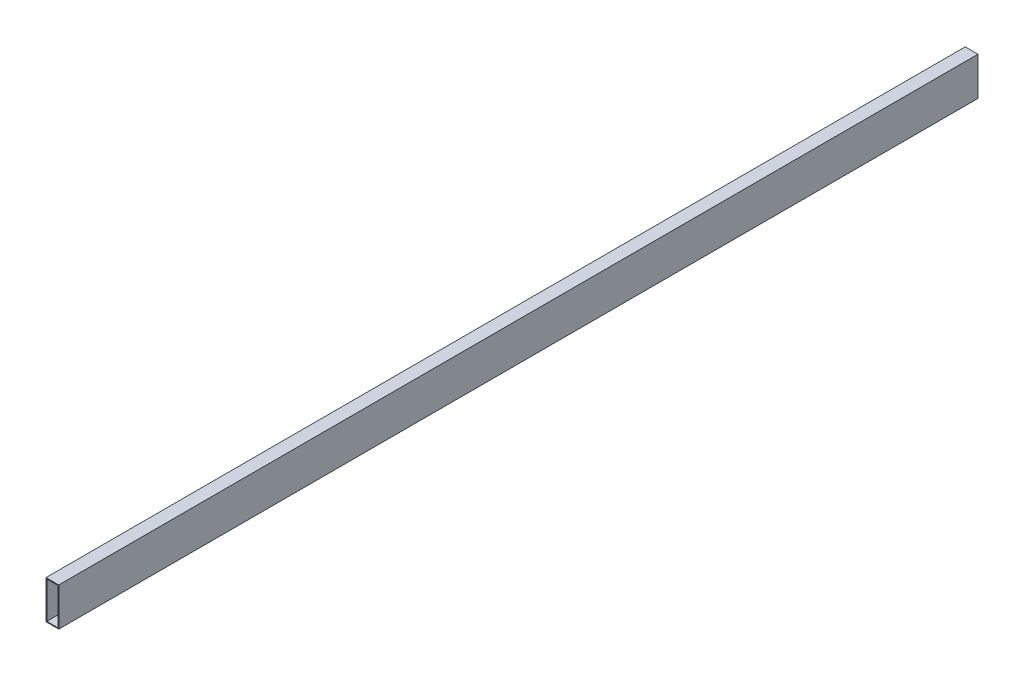
SolidWorks part; units mm, degrees
ref_plane "Front Plane" through (0, 0, 0) normal (0, 0, 1) x (1, 0, 0)
ref_plane "Top Plane" through (0, 0, 0) normal (0, 1, 0) x (1, 0, 0)
ref_plane "Right Plane" through (0, 0, 0) normal (1, 0, 0) x (0, 0, -1)
sketch "Sketch1" plane through (0, 0, 0) normal (0, 0, 1) x (1, 0, 0)
  line L1 (0, 0) -> (50.8, 0)
  line L2 (0, 0) -> (0, 152.4)
  line L3 (0, 152.4) -> (50.8, 152.4)
  line L4 (50.8, 0) -> (50.8, 152.4)
  dimension "D1" = 50.8
  dimension "D2" = 152.4
extrude "Boss-Extrude1" add sketch "Sketch1" along normal blind 3657.6
shell "Shell1" thickness 3.175 removed face at (25.4, 76.2, 3657.6) removed face at (25.4, 76.2, 0)
